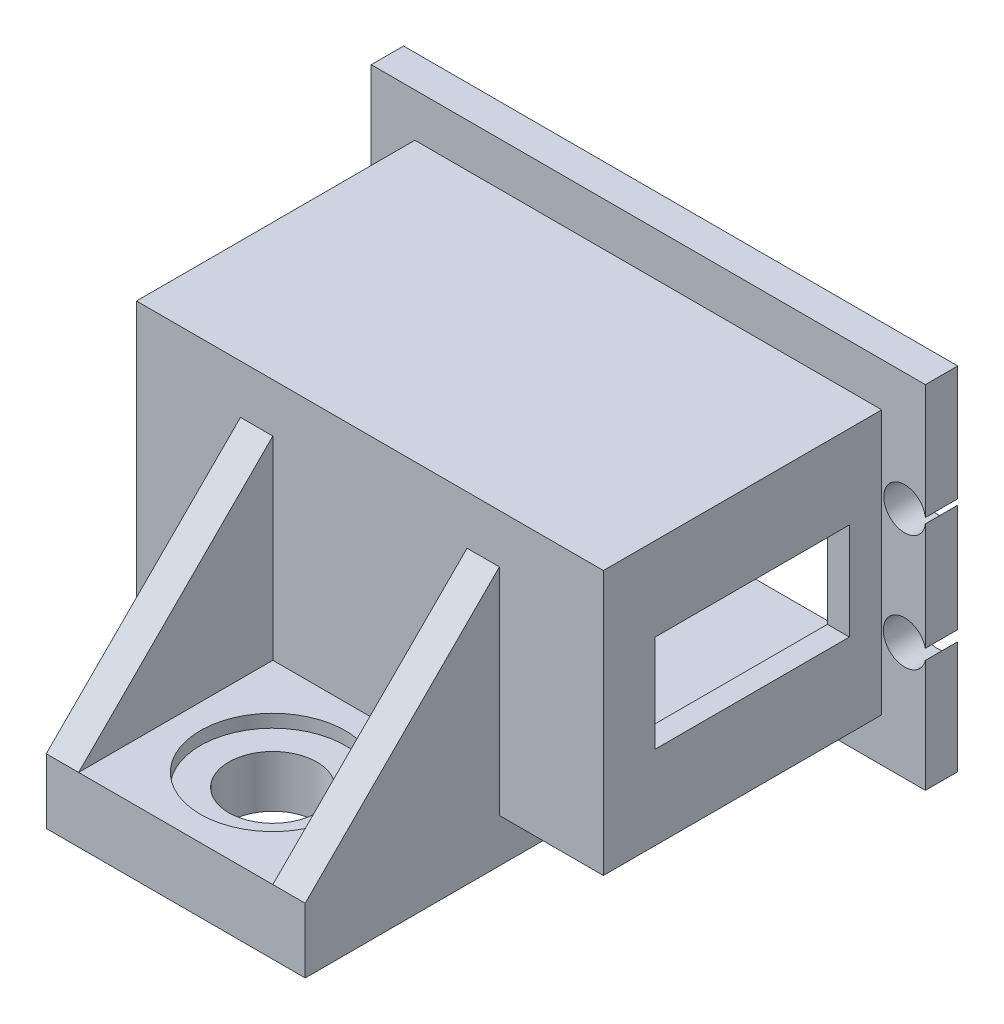
SolidWorks part; units mm, degrees
ref_plane "Front Plane" through (0, 0, 0) normal (0, 0, 1) x (1, 0, 0)
ref_plane "Top Plane" through (0, 0, 0) normal (0, 1, 0) x (1, 0, 0)
ref_plane "Right Plane" through (0, 0, 0) normal (1, 0, 0) x (0, 0, -1)
sketch "Sketch1" plane through (0, 0, 0) normal (0, 0, 1) x (1, 0, 0)
  line L1 (27.178, 17.2339) -> (-27.178, 17.2339)
  line L2 (27.178, 17.2339) -> (27.178, -17.2339)
  line L3 (27.178, -17.2339) -> (-27.178, -17.2339)
  line L4 (-27.178, 17.2339) -> (-27.178, -17.2339)
  line L5 (27.178, 17.2339) -> (-27.178, -17.2339) construction
  line L6 (27.178, -17.2339) -> (-27.178, 17.2339) construction
  line L7 (-27.178, 0) -> (-20.1041, 0) construction
  line L8 (-20.1041, 10.16) -> (-20.1041, -10.16) construction
  line L9 (0, 17.2339) -> (0, 10.16) construction
  line L10 (20.1041, 10.16) -> (-20.1041, 10.16) construction
  line L11 (-27.178, -5.1649) -> (-27.178, 5.1649) construction
  line L13 (20.1041, -10.16) -> (-20.1041, -10.16)
  line L14 (20.1041, -10.16) -> (20.1041, 10.16)
  line L15 (20.1041, 10.16) -> (-20.1041, 10.16)
  line L16 (-20.1041, -10.16) -> (-20.1041, 10.16)
  line L17 (20.1041, -10.16) -> (-20.1041, 10.16) construction
  line L18 (20.1041, 10.16) -> (-20.1041, -10.16) construction
  point P0 (0, 0)
  point P16 (0, 0)
extrude "Boss-Extrude1" add sketch "Sketch1" against normal up to surface (27.94 mm away)
sketch "Sketch2" plane through (0, 0, 0) normal (0, 0, 1) x (1, 0, 0)
  line L0 (20.1041, 10.16) -> (-20.1041, 10.16) construction
  line L1 (22.8981, -12.954) -> (-22.8981, -12.954)
  line L2 (22.8981, -12.954) -> (22.8981, 12.954)
  line L3 (22.8981, 12.954) -> (-22.8981, 12.954)
  line L4 (-22.8981, -12.954) -> (-22.8981, 12.954)
  line L5 (22.8981, -12.954) -> (-22.8981, 12.954) construction
  line L6 (22.8981, 12.954) -> (-22.8981, -12.954) construction
  line L7 (27.178, 17.2339) -> (-27.178, 17.2339)
  line L8 (27.178, 17.2339) -> (27.178, -17.2339)
  line L9 (27.178, -17.2339) -> (-27.178, -17.2339)
  line L10 (-27.178, 17.2339) -> (-27.178, -17.2339)
  line L11 (27.178, 17.2339) -> (-27.178, -17.2339) construction
  line L12 (27.178, -17.2339) -> (-27.178, 17.2339) construction
  line L13 (-20.1041, 10.16) -> (-20.1041, -10.16) construction
  point P0 (0, 0)
  point P6 (0, 0)
  dimension "D1" = 2.794
  dimension "D2" = 2.794
extrude "Cut-Extrude1" cut sketch "Sketch2" against normal offset from surface (24.765 mm away) 3.175 up to face at (0, 0, -27.94)
sketch "Sketch3" plane through (0, 0, -27.94) normal (0, 0, -1) x (-1, 0, 0)
  circle A0 centre (-25.146, 5.6769) radius 2.0497
  circle A1 centre (-25.146, -5.6769) radius 2.0955
  circle A2 centre (25.146, -5.6769) radius 2.0955
  circle A3 centre (25.146, 5.6769) radius 2.0955
extrude "Cut-Extrude2" cut sketch "Sketch3" against normal through all
sketch "Sketch4" plane through (22.8981, 0, 0) normal (1, 0, 0) x (0, 0, -1)
  line L0 (0, -12.954) -> (0, 12.954) construction
  line L1 (2.54, 4.7625) -> (21.59, 4.7625)
  line L2 (2.54, 4.7625) -> (2.54, -4.7625)
  line L3 (2.54, -4.7625) -> (21.59, -4.7625)
  line L4 (21.59, 4.7625) -> (21.59, -4.7625)
  point P4 (2.54, 0)
  dimension "D1" = 19.05
  dimension "D2" = 9.525
  dimension "D3" = 2.54
extrude "Cut-Extrude3" cut sketch "Sketch4" against normal blind 12.7
sketch "Sketch5" plane through (0, 0, 0) normal (0, 0, 1) x (1, 0, 0)
  line L1 (-22.8981, 12.954) -> (22.8981, 12.954)
  line L2 (-22.8981, 12.954) -> (-22.8981, -12.954)
  line L3 (-22.8981, -12.954) -> (22.8981, -12.954)
  line L4 (22.8981, 12.954) -> (22.8981, -12.954)
extrude "Boss-Extrude2" add sketch "Sketch5" along normal blind 2.54
sketch "Sketch6" plane through (0, 0, 2.54) normal (0, 0, 1) x (1, 0, 0)
  line L11 (-22.8981, -12.954) -> (22.8981, -12.954) construction
  line L12 (-12.7, -12.954) -> (12.7, -12.954)
  line L13 (-12.7, -12.954) -> (-12.7, -17.2339)
  line L14 (-12.7, -17.2339) -> (12.7, -17.2339)
  line L15 (12.7, -12.954) -> (12.7, -17.2339)
  line L16 (-27.178, -17.2339) -> (27.178, -17.2339) construction
  point P0 (0, -12.954)
  dimension "D1" = 25.4
extrude "Boss-Extrude3" add sketch "Sketch6" against normal up to surface (27.305 mm away) up to face at (0.0038, 0, -24.765)
sketch "Sketch7" plane through (0, 0, 2.54) normal (0, 0, 1) x (1, 0, 0)
  line L1 (-12.7, -17.2339) -> (12.7, -17.2339)
  line L2 (-12.7, -17.2339) -> (-12.7, -10.8839)
  line L3 (-12.7, -10.8839) -> (12.7, -10.8839)
  line L4 (12.7, -17.2339) -> (12.7, -10.8839)
  dimension "D1" = 25.4
  dimension "D2" = 6.35
extrude "Boss-Extrude4" add sketch "Sketch7" along normal blind 19.05
sketch "Sketch8" plane through (0, -10.8839, 0) normal (0, 1, 0) x (1, 0, 0)
  line L0 (12.7, -21.59) -> (-12.7, -21.59) construction
  line L1 (-12.7, -21.59) -> (-12.7, -2.54) construction
  circle A0 centre (0, -12.065) radius 4.318
  point P4 (0, -21.59)
  point P7 (-12.7, -12.065)
  dimension "D1" = 8.636
extrude "Cut-Extrude4" cut sketch "Sketch8" against normal blind 19.05
sketch "Sketch9" plane through (0, -10.8839, 0) normal (0, 1, 0) x (1, 0, 0)
  circle A0 centre (0, -12.065) radius 7.112
  dimension "D1" = 14.224
extrude "Cut-Extrude5" cut sketch "Sketch9" against normal blind 1.27
sketch "Sketch10" plane through (0, -10.8839, 0) normal (0, 1, 0) x (1, 0, 0)
  line L0 (22.8981, -2.54) -> (-22.8981, -2.54) construction
  line L1 (12.7, -21.59) -> (9.525, -21.59)
  line L2 (12.7, -21.59) -> (12.7, -2.54)
  line L3 (12.7, -2.54) -> (9.525, -2.54)
  line L4 (9.525, -21.59) -> (9.525, -2.54)
  line L6 (-12.7, -21.59) -> (-9.525, -21.59)
  line L7 (-12.7, -21.59) -> (-12.7, -2.54)
  line L8 (-12.7, -2.54) -> (-9.525, -2.54)
  line L9 (-9.525, -21.59) -> (-9.525, -2.54)
  dimension "D1" = 3.175
extrude "Boss-Extrude5" add sketch "Sketch10" along normal blind 19.05
chamfer "Chamfer1" distance 19.05 angle 45 2 edges at (-11.1125, 8.1661, 21.59) (11.1125, 8.1661, 21.59)
sketch "Sketch12" plane through (0, -17.2339, 0) normal (0, -1, 0) x (1, 0, 0)
  line L1 (-3.81, 3.81) -> (3.81, 3.81)
  line L2 (-3.81, 3.81) -> (-3.81, -27.94)
  line L3 (-3.81, -27.94) -> (3.81, -27.94)
  line L4 (3.81, 3.81) -> (3.81, -27.94)
  line L5 (-27.178, -27.94) -> (27.178, -27.94) construction
  point P8 (0, 3.81)
  dimension "D1" = 7.62
  dimension "D2" = 31.75
extrude "Boss-Extrude6" add sketch "Sketch12" along normal blind 3.175
sketch "Sketch13" plane through (0, 0, -27.94) normal (0, 0, -1) x (-1, 0, 0)
  line L0 (-20.1041, 10.16) -> (20.1041, 10.16) construction
  line L1 (20.7391, -10.795) -> (-20.7391, -10.795)
  line L2 (20.7391, -10.795) -> (20.7391, 10.795)
  line L3 (20.7391, 10.795) -> (-20.7391, 10.795)
  line L4 (-20.7391, -10.795) -> (-20.7391, 10.795)
  line L5 (20.7391, -10.795) -> (-20.7391, 10.795) construction
  line L6 (20.7391, 10.795) -> (-20.7391, -10.795) construction
  line L7 (-20.1041, -10.16) -> (-20.1041, 10.16) construction
  point P0 (0, 0)
  dimension "D1" = 0.635
  dimension "D2" = 0.635
extrude "Cut-Extrude7" cut sketch "Sketch13" against normal offset from surface (27.94 mm away) 2.54 up to face at (0, -1.251, 2.54)
